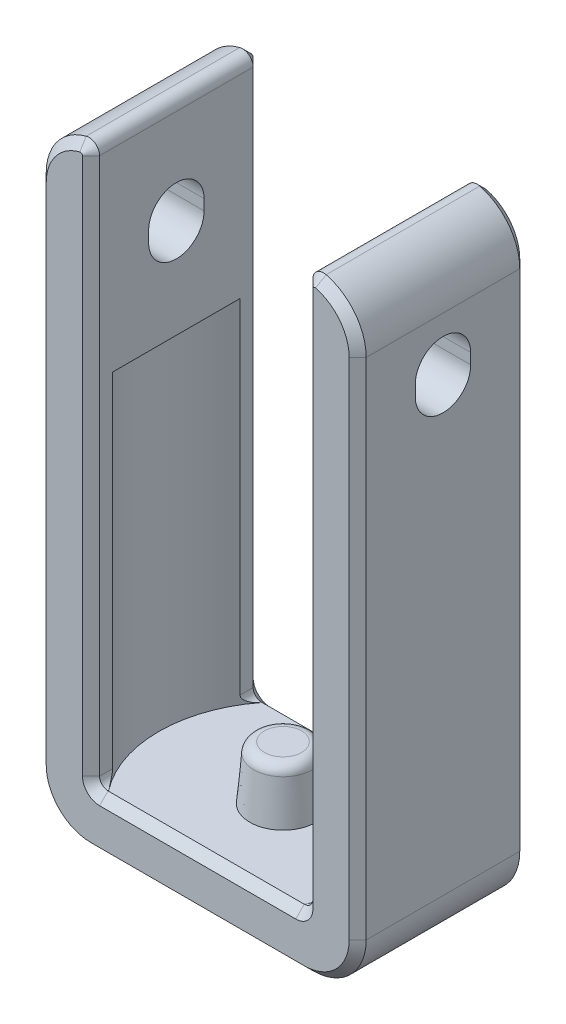
SolidWorks part; units mm, degrees
ref_plane "Front Plane" through (0, 0, 0) normal (0, 0, 1) x (1, 0, 0)
ref_plane "Top Plane" through (0, 0, 0) normal (0, 1, 0) x (1, 0, 0)
ref_plane "Right Plane" through (0, 0, 0) normal (1, 0, 0) x (0, 0, -1)
sketch "Sketch1" plane through (0, 0, 0) normal (0, 0, 1) x (1, 0, 0)
  line L0 (0, 0) -> (0, 57.3)
  line L1 (0, 57.3) -> (5, 57.3)
  line L2 (5, 57.3) -> (5, 5)
  line L3 (5, 5) -> (25, 5)
  line L4 (25, 5) -> (25, 57.3)
  line L5 (25, 57.3) -> (30, 57.3)
  line L6 (30, 57.3) -> (30, 0)
  line L7 (30, 0) -> (0, 0)
  line L9 (5, 5) -> (25, 5) construction
  line L10 (5, 5) -> (5, 57.3) construction
  line L11 (5, 57.3) -> (25, 57.3) construction
  line L12 (25, 5) -> (25, 57.3) construction
  line L13 (5, 5) -> (25, 57.3) construction
  line L14 (5, 57.3) -> (25, 5) construction
  point P3 (15, 31.15)
  dimension "D1" = 20
  dimension "D2" = 52.3
  dimension "D3" = 5
  dimension "D4" = 5
extrude "Boss-Extrude1" add sketch "Sketch1" along normal blind 16
fillet "Fillet3" radius 0.8 2 edges at (5, 5, 8) (25, 5, 8)
sketch "Sketch3" plane through (0, 0, 0) normal (0, 1, 0) x (1, 0, 0)
  line L0 (15, 0) -> (15, -16) construction
  line L1 (24.2, 0) -> (5.8, 0) construction
  line L2 (24.2, -16) -> (5.8, -16) construction
  line L3 (30, -8) -> (0, -8) construction
  line L4 (30, -16) -> (30, 0) construction
  line L5 (0, -16) -> (0, 0) construction
  circle A0 centre (15, -8) radius 11.65
  dimension "D1" = 23.3
extrude "Cut-Extrude1" cut sketch "Sketch3" along normal blind 33 from surface contours A0 starting at face at (15, 5, 8)
sketch "Sketch2" plane through (0, 5, 0) normal (0, 1, 0) x (1, 0, 0)
  line L0 (15, 0) -> (15, -16) construction
  line L1 (24.2, 0) -> (5.8, 0) construction
  line L2 (24.2, -16) -> (5.8, -16) construction
  circle A0 centre (15, -8) radius 3.1
  dimension "D1" = 6.2
extrude "Boss-Extrude2" add sketch "Sketch2" along normal blind 5 draft 5
sketch "Sketch4" plane through (0, 0, 0) normal (0, 0, 1) x (1, 0, 0)
  line L0 (25, 57.3) -> (25, 5.8) construction
  line L1 (5, 5) -> (25, 5) construction
  line L2 (5, 5) -> (5, 37.2) construction
  line L3 (5, 37.2) -> (25, 37.2) construction
  line L4 (25, 5) -> (25, 37.2) construction
  line L5 (15, 37.2) -> (15, 47.2) construction
  line L6 (5, 38) -> (5, 5.8) construction
  line L7 (5, 37.2) -> (25, 37.2) construction
  line L8 (5, 37.2) -> (5, 57.2) construction
  line L9 (5, 57.2) -> (25, 57.2) construction
  line L10 (25, 37.2) -> (25, 57.2) construction
  line L11 (5, 37.2) -> (25, 57.2) construction
  line L12 (5, 57.2) -> (25, 37.2) construction
  line L13 (18.1, 5) -> (11.9, 5) construction
  dimension "D1" = 32.2
  dimension "D2" = 10
  dimension "D3" = 20
  dimension "D4" = 20
sketch "Sketch5" plane through (30, 0, 0) normal (1, 0, 0) x (0, 0, -1)
  line L0 (-8, 57.3) -> (-8, 0) construction
  line L1 (-16, 57.3) -> (0, 57.3) construction
  line L2 (-16, 0) -> (0, 0) construction
  line L3 (-8, 47.8) -> (-8, 46.8) construction
  line L4 (-5.4, 47.8) -> (-5.4, 46.8)
  line L5 (-10.6, 47.8) -> (-10.6, 46.8)
  arc A0 (-5.4, 47.8) -> (-10.6, 47.8) centre (-8, 47.8) ccw
  arc A1 (-10.6, 46.8) -> (-5.4, 46.8) centre (-8, 46.8) ccw
  point P8 (-8, 47.3)
  dimension "D1" = 2.6
  dimension "D2" = 10
  dimension "D3" = 1
extrude "Cut-Extrude2" cut sketch "Sketch5" against normal through all
fillet "Fillet1" radius 5 4 edges at (0, 0, 8) (30, 0, 8) (30, 57.3, 8) (0, 57.3, 8)
fillet "Fillet2" radius 1 3 edges at (15, 10, 10.6626) (25, 57.3, 8) (5, 57.3, 8)
chamfer "Chamfer2" distance 0.8 angle 45 28 edges at (24.7657, 5.2343, 0) (15, 5, 0) (5.2343, 5.2343, 0) (5, 30.9865, 0) (1.0472, 55.3619, 0) (0, 28.65, 0) (1.4645, 1.4645, 0) (15, 0, 0) (28.5355, 1.4645, 0) (30, 28.65, 0) (28.9528, 55.3619, 0) (25, 30.9865, 0) (28.5355, 1.4645, 16) (15, 0, 16) (1.4645, 1.4645, 16) (0, 28.65, 16) (1.0472, 55.3619, 16) (5, 30.9865, 16) (5.2343, 5.2343, 16) (15, 5, 16) (24.7657, 5.2343, 16) (25, 30.9865, 16) (28.9528, 55.3619, 16) (30, 28.65, 16) (4.6124, 56.9636, 0) (25.3876, 56.9636, 0) (4.6124, 56.9636, 16) (25.3876, 56.9636, 16)
